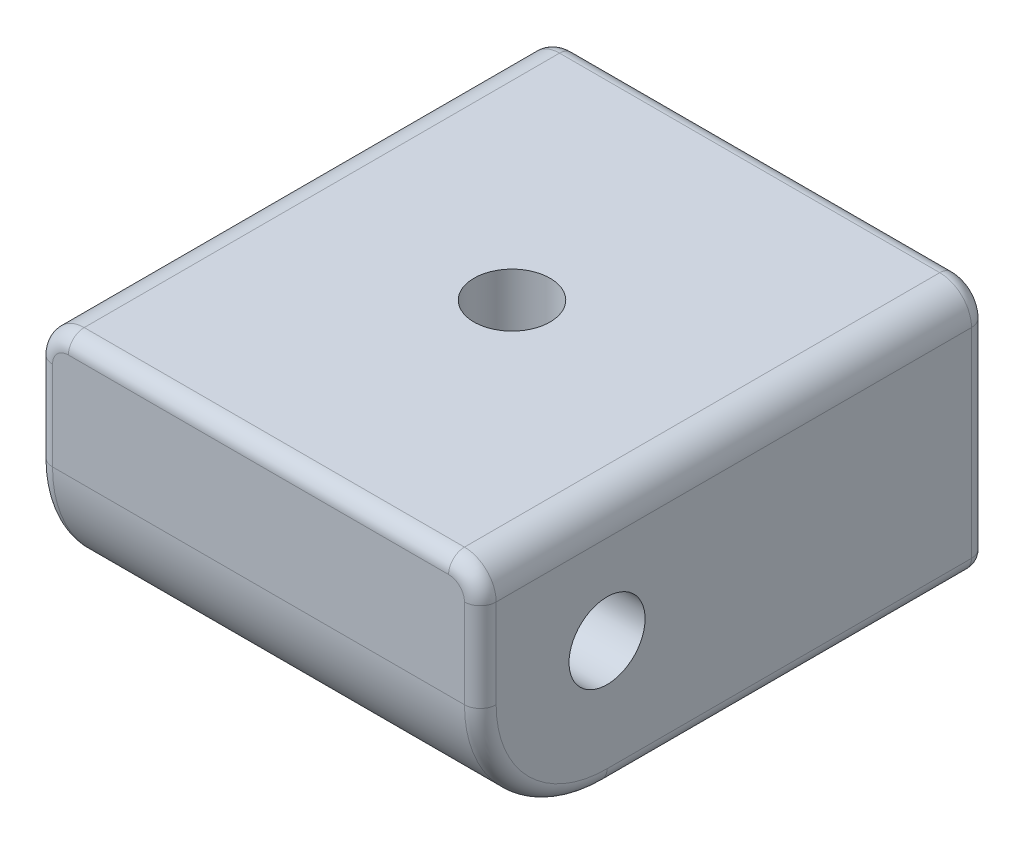
SolidWorks part; units mm, degrees
ref_plane "Front Plane" through (0, 0, 0) normal (0, 0, 1) x (1, 0, 0)
ref_plane "Top Plane" through (0, 0, 0) normal (0, 1, 0) x (1, 0, 0)
ref_plane "Right Plane" through (0, 0, 0) normal (1, 0, 0) x (0, 0, -1)
sketch "Sketch1" plane through (0, 0, 0) normal (0, 0, 1) x (1, 0, 0)
  line L0 (-11.1125, 0) -> (11.1125, 0)
  line L1 (11.1125, 0) -> (11.1125, 10.8077)
  line L2 (9.525, 12.3952) -> (-9.525, 12.3952)
  line L3 (-11.1125, 10.8077) -> (-11.1125, 0)
  circle A0 centre (-6.35, 6.35) radius 1.905
  circle A1 centre (6.35, 6.35) radius 1.905
  arc A2 (11.1125, 10.8077) -> (9.525, 12.3952) centre (9.525, 10.8077) ccw
  arc A3 (-9.525, 12.3952) -> (-11.1125, 10.8077) centre (-9.525, 10.8077) ccw
  point P4 (0, 0)
  point P15 (-11.1125, 12.3952)
  dimension "D6" = 1.5875
  dimension "D7" = 3.81
  dimension "D1" = 22.225
  dimension "D2" = 12.3952
  dimension "D3" = 12.7
  dimension "D4" = 6.35
  dimension "D5" = 4.7625
extrude "Boss-Extrude1" add sketch "Sketch1" along normal blind 12.7
sketch "Sketch2" plane through (0, 0, 12.7) normal (0, 0, 1) x (1, 0, 0)
  line L4 (11.1125, 0) -> (11.1125, 10.8077)
  line L5 (9.525, 12.3952) -> (-9.525, 12.3952)
  line L6 (-11.1125, 10.8077) -> (-11.1125, 0)
  line L7 (-11.1125, 0) -> (11.1125, 0)
  line L8 (11.1125, 0) -> (11.1125, 10.8077)
  line L9 (9.525, 12.3952) -> (-9.525, 12.3952)
  line L10 (-11.1125, 10.8077) -> (-11.1125, 0)
  line L11 (-11.1125, 0) -> (11.1125, 0)
  arc A2 (11.1125, 10.8077) -> (9.525, 12.3952) centre (9.525, 10.8077) ccw
  arc A3 (-9.525, 12.3952) -> (-11.1125, 10.8077) centre (-9.525, 10.8077) ccw
  arc A4 (11.1125, 10.8077) -> (9.525, 12.3952) centre (9.525, 10.8077) ccw
  arc A5 (-9.525, 12.3952) -> (-11.1125, 10.8077) centre (-9.525, 10.8077) ccw
  dimension "D1" = 0
extrude "Boss-Extrude2" add sketch "Sketch2" along normal blind 12.7
sketch "Sketch3" plane through (11.1125, 0, 0) normal (1, 0, 0) x (0, 0, -1)
  line L0 (-25.4, 0) -> (0, 0) construction
  line L1 (-25.4, 0) -> (-25.4, 10.8077) construction
  circle A0 centre (-19.05, 6.35) radius 1.905
  dimension "D3" = 3.81
  dimension "D1" = 6.35
  dimension "D2" = 6.35
extrude "Cut-Extrude1" cut sketch "Sketch3" against normal up to next
sketch "Sketch4" plane through (0, 12.3952, 0) normal (0, 1, 0) x (1, 0, 0)
  line L0 (9.525, 0) -> (-9.525, 0) construction
  circle A0 centre (0, -12.7) radius 1.905
  point P4 (0, 0)
  dimension "D2" = 3.81
  dimension "D1" = 12.7
extrude "Cut-Extrude2" cut sketch "Sketch4" against normal offset from surface (10.8077 mm away) 1.5875 up to face at (0, 0, 12.7)
fillet "Fillet1" radius 0.7937 13 edges at (11.1125, 5.4038, 0) (10.6475, 11.9302, 0) (-11.1125, 5.4038, 0) (-10.6475, 11.9302, 0) (-11.1125, 0, 12.7) (11.1125, 0, 12.7) (0, 0, 0) (-11.1125, 5.4038, 25.4) (-10.6475, 11.9302, 25.4) (0, 12.3952, 25.4) (10.6475, 11.9302, 25.4) (11.1125, 5.4038, 25.4) (0, 12.3952, 0)
fillet "Fillet2" radius 6.35 3 edges at (10.88, 0.2325, 25.1675) (-10.88, 0.2325, 25.1675) (0, 0, 25.4)
